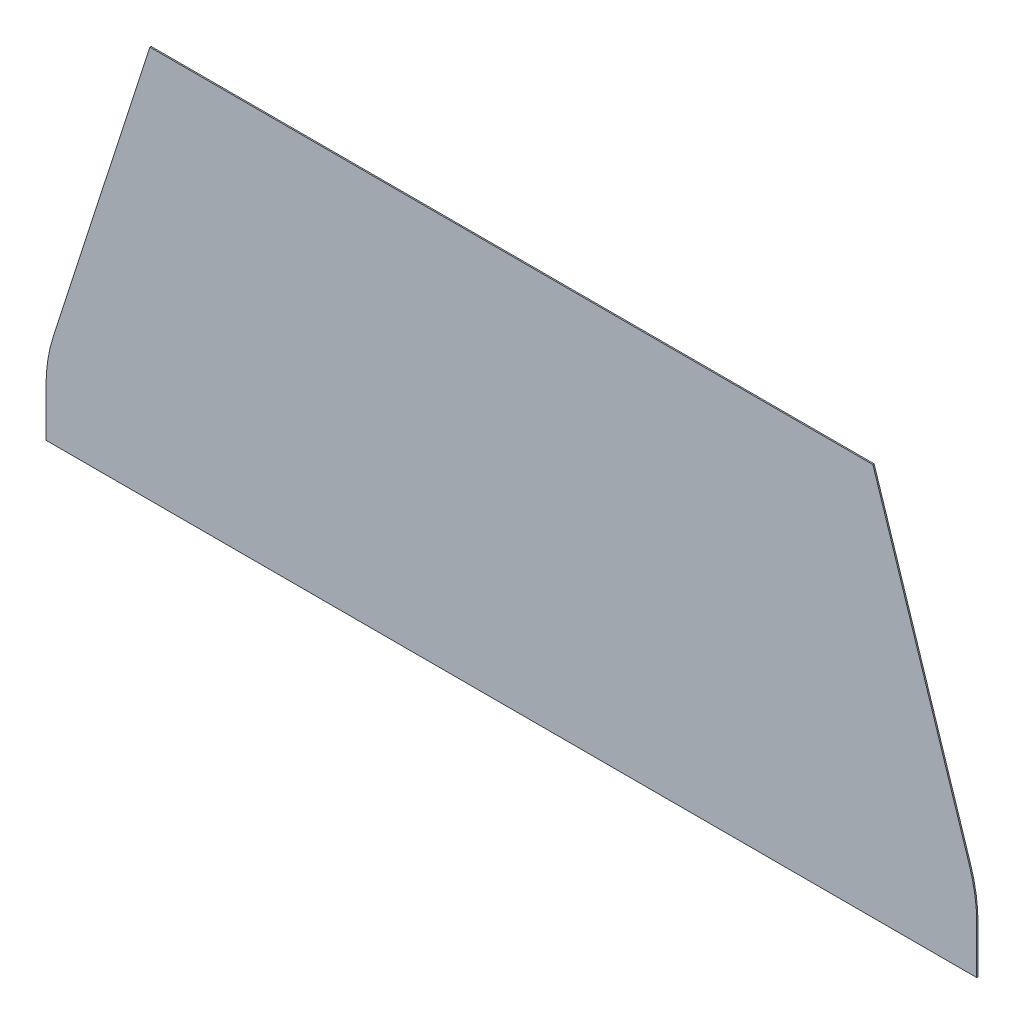
SolidWorks part; units mm, degrees
material "5052-O"
ref_plane "Front Plane" through (0, 0, 0) normal (0, 0, 1) x (1, 0, 0)
ref_plane "Top Plane" through (0, 0, 0) normal (0, 1, 0) x (1, 0, 0)
ref_plane "Right Plane" through (0, 0, 0) normal (1, 0, 0) x (0, 0, -1)
sketch "Sketch1" plane through (0, 0, 0) normal (0, 0, 1) x (1, 0, 0)
  line L0 (-370, 37.5704) -> (-370, 0)
  line L1 (-370, 0) -> (370, 0)
  line L2 (370, 0) -> (370, 37.5704)
  line L3 (-364.1849, 74.4731) -> (-287.42, 312)
  line L4 (-287.42, 312) -> (287.42, 312)
  line L5 (287.42, 312) -> (364.1849, 74.4731)
  arc A0 (370, 37.5704) -> (364.1849, 74.4731) centre (250, 37.5704) ccw
  arc A1 (-364.1849, 74.4731) -> (-370, 37.5704) centre (-250, 37.5704) ccw
  point P2 (0, 0)
  point P5 (0, 312)
  dimension "D5" = 120
  dimension "D1" = 17.91
  dimension "D2" = 574.84
  dimension "D3" = 312
  dimension "D4" = 740
base flange "Top Firewall" sketch "Sketch1" thickness 1 reverse thickness direction no parameters "D1"=0.7366
sketch "Bend-Lines1" [suppressed] plane through (0, 0, 0) normal (0, 1, 0) x (1, 0, 0)
sketch "Bounding-Box1" [suppressed] plane through (0, 0, 0) normal (0, 1, 0) x (1, 0, 0)
sheet metal parameters "Sheet-Metal1" thickness 1 parameters "D1"=0.7366
flat pattern "Flat-Pattern1" [suppressed]
sketch "Bend-Lines2" plane through (0, 0, 0) normal (0, 1, 0) x (1, 0, 0)
sketch3d "Bounding-Box2" [suppressed]
  line L0 (619.9862, 274.4587, 0) -> (-120.0121, 274.426, 0) construction
  line L1 (620, -37.5376, 0) -> (-119.9983, -37.5704, 0) construction
  line L2 (619.9862, 274.4587, 0) -> (620, -37.5376, 0) construction
  line L3 (-120.0121, 274.426, 0) -> (-119.9983, -37.5704, 0) construction
